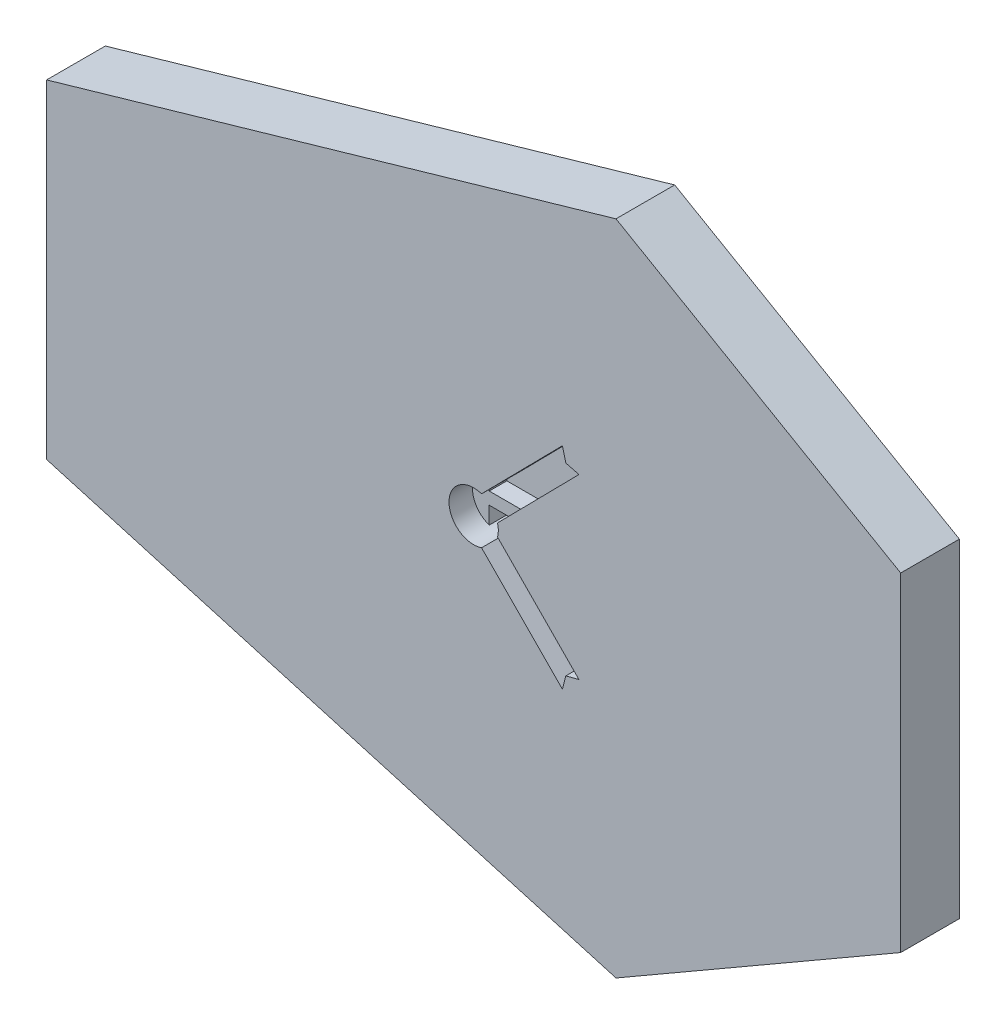
SolidWorks part; units mm, degrees
ref_plane "Front Plane" through (0, 0, 0) normal (0, 0, 1) x (1, 0, 0)
ref_plane "Top Plane" through (0, 0, 0) normal (0, 1, 0) x (1, 0, 0)
ref_plane "Right Plane" through (0, 0, 0) normal (1, 0, 0) x (0, 0, -1)
sketch "Sketch2" plane through (0, 0, 0) normal (0, 0, 1) x (1, 0, 0)
  line L0 (-41.5231, 14) -> (-41.5231, -14) construction
  line L1 (6.9744, -28) -> (-41.5231, -14) construction
  line L2 (6.9744, -28) -> (31.2231, -14) construction
  line L3 (31.2231, -14) -> (31.2231, 14) construction
  line L4 (31.2231, 14) -> (6.9744, 28) construction
  line L5 (-41.5231, 14) -> (6.9744, 28) construction
  line L6 (-41.5231, 14) -> (-41.5231, -14)
  line L7 (6.9744, -28) -> (-41.5231, -14)
  line L8 (6.9744, -28) -> (31.2231, -14)
  line L9 (31.2231, -14) -> (31.2231, 14)
  line L10 (31.2231, 14) -> (6.9744, 28)
  line L11 (-41.5231, 14) -> (6.9744, 28)
extrude "Boss-Extrude1" add sketch "Sketch2" along normal blind 1.5
sketch "Sketch4" plane through (0, 0, 1.5) normal (0, 0, 1) x (1, 0, 0)
  line L6 (6.9744, 28) -> (-41.5231, 14)
  line L7 (-41.5231, 14) -> (-41.5231, -14)
  line L8 (-41.5231, -14) -> (6.9744, -28)
  line L9 (6.9744, -28) -> (31.2231, -14)
  line L10 (31.2231, -14) -> (31.2231, 14)
  line L11 (31.2231, 14) -> (6.9744, 28)
  line L12 (6.9744, 28) -> (-41.5231, 14)
  line L13 (-41.5231, 14) -> (-41.5231, -14)
  line L14 (-41.5231, -14) -> (6.9744, -28)
  line L15 (6.9744, -28) -> (31.2231, -14)
  line L16 (31.2231, -14) -> (31.2231, 14)
  line L17 (31.2231, 14) -> (6.9744, 28)
  circle A0 centre (-5.15, 0) radius 2.1
  point P9 (-5.15, 0)
  dimension "D2" = 4.2
  dimension "D1" = 0
extrude "Boss-Extrude2" add sketch "Sketch4" along normal blind 3.5
sketch "Sketch5" plane through (0, 0, 5) normal (0, 0, 1) x (1, 0, 0)
  line L0 (-13.0004, 7.8504) -> (-16.8732, 6.8495) construction
  line L1 (-16.8732, 6.8495) -> (-16.1225, 3.9449) construction
  line L2 (-10.5382, 5.3882) -> (-16.1225, 3.9449) construction
  line L3 (-9.0949, 10.9725) -> (-10.5382, 5.3882) construction
  line L4 (-11.9995, 11.7232) -> (-9.0949, 10.9725) construction
  line L5 (-11.9995, 11.7232) -> (-13.0004, 7.8504) construction
  line L6 (-13.0004, 7.8504) -> (-16.8732, 6.8495) construction
  line L7 (-16.8732, 6.8495) -> (-16.1225, 3.9449) construction
  line L8 (-10.5382, 5.3882) -> (-16.1225, 3.9449) construction
  line L9 (-9.0949, 10.9725) -> (-10.5382, 5.3882) construction
  line L10 (-11.9995, 11.7232) -> (-9.0949, 10.9725) construction
  line L11 (-11.9995, 11.7232) -> (-13.0004, 7.8504) construction
  line L12 (-7.184, 0.5223) -> (-14.1193, 7.5613) construction
  line L13 (-14.1193, 7.5613) -> (-13.0004, 7.8504) construction
  line L14 (-12.7087, 8.9791) -> (-5.8221, 1.9895) construction
  line L15 (-13.0004, 7.8504) -> (-12.7087, 8.9791) construction
  line L16 (-6.4, 3.7) -> (-3.9, -3.7) construction
  line L17 (-5.15, 0) -> (-5.15, 24.5) construction
  line L18 (-12.7087, 8.9791) -> (-14.1193, 7.5613) construction
  line L19 (-13.414, 8.2702) -> (-13.0004, 7.8504) construction
  line L20 (-7.184, 0.5223) -> (-4.4779, 0.5223) construction
  line L21 (-4.4779, 0.5223) -> (-4.4779, 1.9895) construction
  line L22 (-4.4779, 1.9895) -> (-5.8221, 1.9895)
  line L23 (6.9744, 28) -> (-41.5231, 14) construction
  line L24 (3.114, 8.2702) -> (2.7004, 7.8504) construction
  line L25 (2.4087, 8.9791) -> (3.8193, 7.5613) construction
  line L26 (1.6995, 11.7232) -> (2.7004, 7.8504) construction
  line L27 (1.6995, 11.7232) -> (-1.2051, 10.9725) construction
  line L28 (-1.2051, 10.9725) -> (0.2382, 5.3882) construction
  line L29 (0.2382, 5.3882) -> (5.8225, 3.9449) construction
  line L30 (6.5732, 6.8495) -> (5.8225, 3.9449) construction
  line L31 (2.7004, 7.8504) -> (6.5732, 6.8495) construction
  line L32 (-5.8221, 0.5223) -> (-5.8221, 1.9895)
  line L33 (-3.116, 0.5223) -> (-5.8221, 0.5223)
  line L34 (2.7004, 7.8504) -> (2.4087, 8.9791)
  line L35 (2.4087, 8.9791) -> (-4.4779, 1.9895)
  line L36 (3.8193, 7.5613) -> (2.7004, 7.8504)
  line L37 (-3.116, 0.5223) -> (3.8193, 7.5613)
  circle A0 centre (-5.15, 0) radius 2.1 construction
  dimension "D1" = 2
extrude "Cut-Extrude1" cut sketch "Sketch5" against normal up to surface (3.5 mm away) up to face at (-3.05, 0, 1.5)
sketch "Sketch9" plane through (0, 0, 1.5) normal (0, 0, 1) x (1, 0, 0)
  line L8 (2.4087, 8.9791) -> (2.7004, 7.8504)
  line L9 (2.7004, 7.8504) -> (3.8193, 7.5613)
  line L10 (3.8193, 7.5613) -> (2.009, 5.7239)
  line L11 (-3.116, 0.5223) -> (3.8193, 7.5613) construction
  line L12 (2.009, 5.7239) -> (0.5844, 7.1276)
  line L13 (2.4087, 8.9791) -> (-4.4779, 1.9895) construction
  line L14 (0.5844, 7.1276) -> (2.4087, 8.9791)
  dimension "D1" = 2
extrude "Cut-Extrude2" cut sketch "Sketch9" against normal through all
sketch "Sketch7" plane through (0, 0, 5) normal (0, 0, 1) x (1, 0, 0)
  line L0 (-7.25, 0) -> (-3.05, 0) construction
  line L1 (-5.15, 2.1) -> (-5.15, -2.1) construction
  arc A0 (-4.4779, 1.9895) -> (-3.116, 0.5223) centre (-5.15, 0) ccw construction
ref_plane "Plane1" through (0, 0, 0) normal (0, -1, 0) x (1, 0, 0)
mirror "Mirror1" about plane through (0, 0, 0) normal (0, -1, 0) of "Cut-Extrude2", "Cut-Extrude1"
sketch "Sketch8" plane through (0, 0, 1.5) normal (0, 0, 1) x (1, 0, 0)
  line L2 (-5.8221, 0.5223) -> (-5.8221, 1.9895) construction
  line L3 (-3.116, 0.5223) -> (-5.8221, 0.5223) construction
  line L4 (-5.8221, 0.5223) -> (-5.8221, 1.9895)
  line L5 (-3.116, 0.5223) -> (-5.8221, 0.5223)
  line L6 (-7.25, 0) -> (-3.05, 0) construction
  line L7 (-3.116, -0.5223) -> (-5.8221, -0.5223)
  line L8 (-5.8221, -0.5223) -> (-5.8221, -1.9895)
  arc A0 (-3.116, -0.5223) -> (-3.116, 0.5223) centre (-5.15, 0) ccw construction
  arc A1 (-3.116, -0.5223) -> (-3.116, 0.5223) centre (-5.15, 0) ccw
  arc A2 (-4.4779, 1.9895) -> (-4.4779, -1.9895) centre (-5.15, 0) ccw construction
  arc A3 (-5.8221, 1.9895) -> (-5.8221, -1.9895) centre (-5.15, 0) ccw
extrude "Boss-Extrude3" add sketch "Sketch8" along normal blind 1.5
